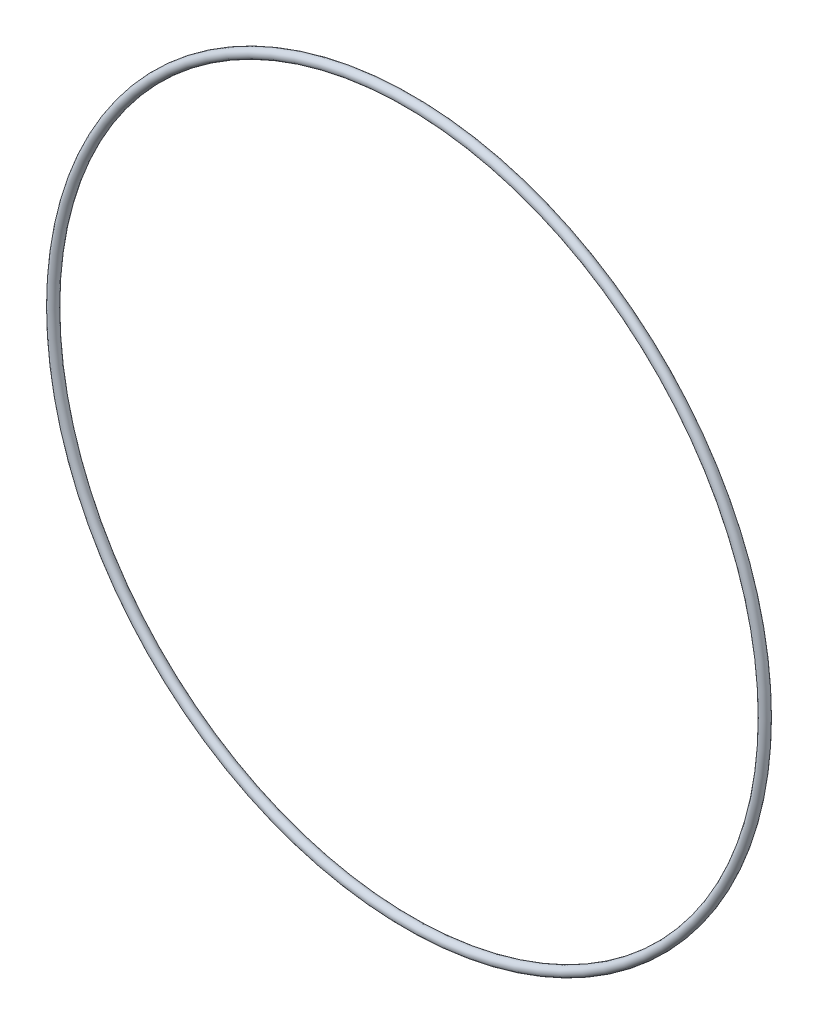
SolidWorks part; units mm, degrees
ref_plane "Front" through (0, 0, 0) normal (0, 0, 1) x (1, 0, 0)
ref_plane "Top" through (0, 0, 0) normal (0, 1, 0) x (1, 0, 0)
ref_plane "Right" through (0, 0, 0) normal (1, 0, 0) x (0, 0, -1)
sketch "Sketch1" plane through (0, 0, 0) normal (1, 0, 0) x (0, -1, 0)
  line L0 (0, -0.889) -> (0, 0.889) construction
  line L2 (-75.1446, 0) -> (75.1446, 0) construction
  line L3 (-66.5353, 0) -> (66.5353, 0) construction
  circle A0 centre (67.4243, 0) radius 0.889
  point P9 (66.5353, 0)
  point P10 (68.3133, 0)
  point P13 (67.4243, 0.889)
  point P14 (67.4243, -0.889)
  dimension "Width" = 1.778
  dimension "ID" = 133.0706
revolve "Revolve1" add sketch "Sketch1" angle 360 about L0
ref_axis "Axis1" through (0, 0, 0.9779) along (0, 0, -1)
